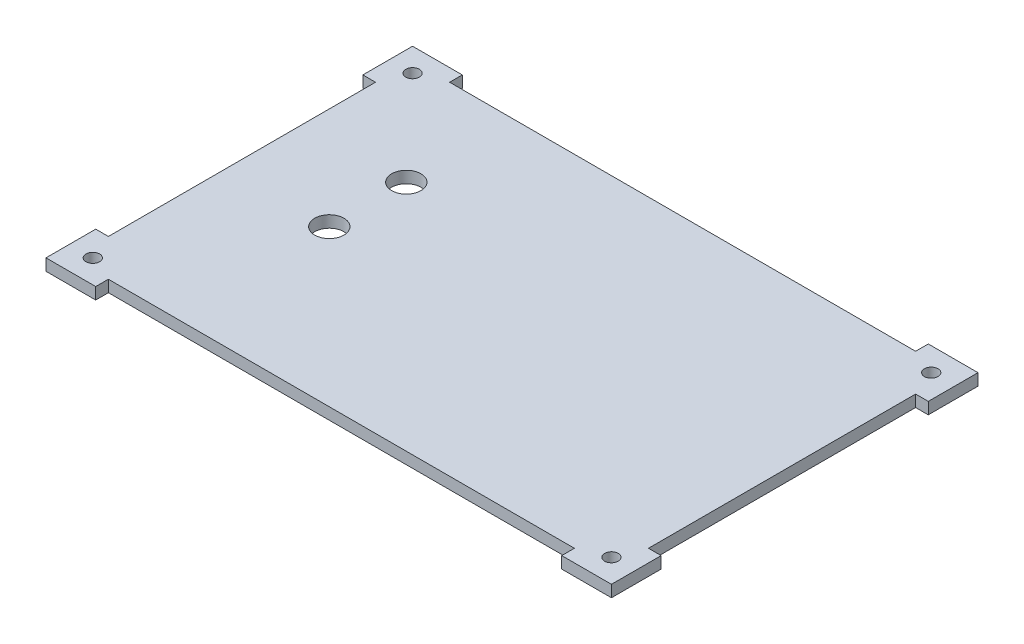
SolidWorks part; units mm, degrees
material "Perspex (TM) GS Acrylic Cast Sheet"
ref_plane "Front Plane" through (0, 0, 0) normal (0, 0, 1) x (1, 0, 0)
ref_plane "Top Plane" through (0, 0, 0) normal (0, 1, 0) x (1, 0, 0)
ref_plane "Right Plane" through (0, 0, 0) normal (1, 0, 0) x (0, 0, -1)
sketch "Sketch1" plane through (0, 0, 0) normal (0, 1, 0) x (1, 0, 0)
  line L1 (0, 0) -> (138.5, 0)
  line L2 (0, 0) -> (0, -87.5)
  line L3 (0, -87.5) -> (138.5, -87.5)
  line L4 (138.5, 0) -> (138.5, -87.5)
  dimension "D1" = 138.5
  dimension "D2" = 87.5
extrude "Boss-Extrude1" add sketch "Sketch1" along normal blind 3
sketch "Sketch2" plane through (0, 0, 0) normal (0, -1, 0) x (1, 0, 0)
  line L0 (0, 0) -> (0, 87.5) construction
  line L1 (0, 87.5) -> (138.5, 87.5) construction
  line L2 (138.5, 0) -> (0, 0) construction
  line L3 (138.5, 87.5) -> (138.5, 0) construction
  circle A0 centre (2.75, 84.75) radius 1.75
  circle A1 centre (135.75, 84.75) radius 1.75
  circle A2 centre (135.75, 2.75) radius 1.75
  circle A3 centre (2.75, 2.75) radius 1.75
  dimension "D1" = 3.5
  dimension "D2" = 2.75
  dimension "D3" = 2.75
  dimension "D4" = 2.75
  dimension "D5" = 2.75
  dimension "D6" = 2.75
  dimension "D7" = 2.75
  dimension "D8" = 2.75
  dimension "D9" = 2.75
extrude "Cut-Extrude1" cut sketch "Sketch2" against normal through all
sketch "Sketch3" plane through (0, 0, 0) normal (0, -1, 0) x (1, 0, 0)
  line L0 (0, 0) -> (0, 87.5) construction
  line L1 (-3.25, 90.75) -> (0, 90.75)
  line L2 (-3.25, 90.75) -> (-3.25, 78)
  line L3 (-3.25, 78) -> (0, 78)
  line L4 (0, 90.75) -> (0, 78)
  line L5 (0, 87.5) -> (138.5, 87.5) construction
  line L6 (0, 90.75) -> (9.5, 90.75)
  line L7 (0, 90.75) -> (0, 87.5)
  line L8 (0, 87.5) -> (9.5, 87.5)
  line L9 (9.5, 90.75) -> (9.5, 87.5)
  line L10 (138.5, 87.5) -> (138.5, 0) construction
  line L11 (138.5, 87.5) -> (129, 87.5)
  line L12 (138.5, 87.5) -> (138.5, 90.75)
  line L13 (138.5, 90.75) -> (129, 90.75)
  line L14 (129, 87.5) -> (129, 90.75)
  line L15 (138.5, 90.75) -> (141.75, 90.75)
  line L16 (138.5, 90.75) -> (138.5, 78)
  line L17 (138.5, 78) -> (141.75, 78)
  line L18 (141.75, 90.75) -> (141.75, 78)
  line L19 (138.5, 0) -> (0, 0) construction
  line L20 (0, 0) -> (-3.25, 0)
  line L21 (0, 0) -> (0, 9.5)
  line L22 (0, 9.5) -> (-3.25, 9.5)
  line L23 (-3.25, 0) -> (-3.25, 9.5)
  line L24 (-3.25, 0) -> (9.5, 0)
  line L25 (-3.25, 0) -> (-3.25, -3.25)
  line L26 (-3.25, -3.25) -> (9.5, -3.25)
  line L27 (9.5, 0) -> (9.5, -3.25)
  line L29 (138.5, 0) -> (141.75, 0)
  line L30 (138.5, 0) -> (138.5, 9.5)
  line L31 (138.5, 9.5) -> (141.75, 9.5)
  line L32 (141.75, 0) -> (141.75, 9.5)
  line L33 (141.75, 0) -> (129, 0)
  line L34 (141.75, 0) -> (141.75, -3.25)
  line L35 (141.75, -3.25) -> (129, -3.25)
  line L36 (129, 0) -> (129, -3.25)
  line M11 (0, 87.5) -> (0, 0)
  line M12 (0, 0) -> (138.5, 0)
  line M13 (138.5, 0) -> (138.5, 87.5)
  line M14 (138.5, 87.5) -> (0, 87.5)
  dimension "D1" = 9.5
  dimension "D2" = 9.5
  dimension "D3" = 3.25
  dimension "D4" = 3.25
  dimension "D5" = 3.25
  dimension "D6" = 3.25
  dimension "D7" = 9.5
  dimension "D8" = 9.5
  dimension "D9" = 3.25
  dimension "D10" = 3.25
  dimension "D11" = 9.5
  dimension "D12" = 9.5
  dimension "D13" = 3.25
  dimension "D14" = 3.25
  dimension "D15" = 9.5
  dimension "D16" = 9.5
extrude "Boss-Extrude2" add sketch "Sketch3" against normal through all contours L4 L1 L2 L3 M11 | L9 L6 L4 M14 | L23 L20 L22 M11 | L27 L20 L25 L26 M12 | L36 L35 L34 L29 M12 | L29 L32 L31 M13 | L14 L12 L13 M14 | L18 L15 L12 L17 M13 region at (-1.625, 0, 84.375) region at (4.75, 0, 89.125) region at (-1.625, 0, 4.75) region at (133.75, 0, 89.125) region at (3.125, 0, -1.625) region at (140.125, 0, 84.375) region at (135.375, 0, -1.625) region at (140.125, 0, 4.75)
sketch "Sketch4" plane through (0, 0, 0) normal (0, -1, 0) x (1, 0, 0)
  line L0 (0, 9.5) -> (0, 78) construction
  line L1 (9.5, 87.5) -> (129, 87.5) construction
  circle A0 centre (26.15, 47.5) radius 3.75
  circle A1 centre (26.15, 27.75) radius 3.75
  dimension "D1" = 7.5
  dimension "D2" = 7.5
  dimension "D3" = 26.15
  dimension "D4" = 40
  dimension "D5" = 26.15
  dimension "D6" = 19.75
extrude "Cut-Extrude2" cut sketch "Sketch4" against normal through all
equation "\"D4@Sketch2\"=\"D2@Sketch2\""
equation "\"D5@Sketch2\"=\"D4@Sketch2\""
equation "\"D6@Sketch2\"=\"D5@Sketch2\""
equation "\"D7@Sketch2\"=\"D6@Sketch2\""
equation "\"D8@Sketch2\"=\"D2@Sketch2\""
equation "\"D9@Sketch2\"=\"D8@Sketch2\""
equation "\"D2@Sketch4\"=\"D1@Sketch4\""
equation "\"D5@Sketch4\"=\"D3@Sketch4\""
